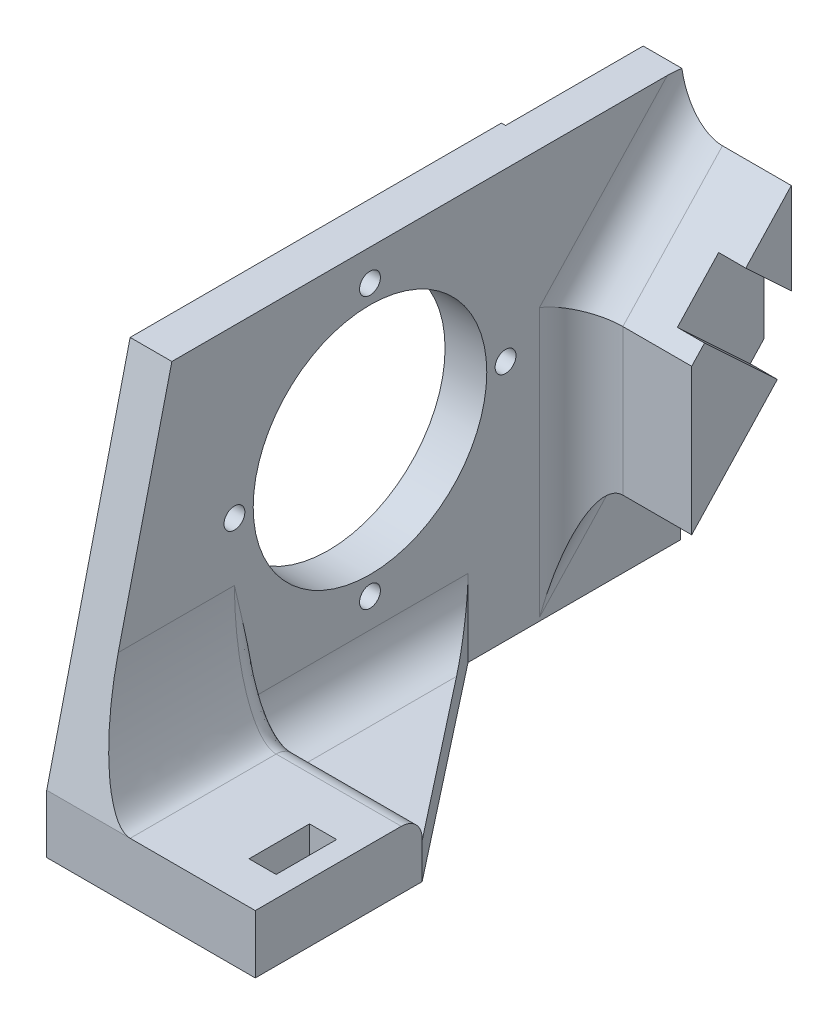
SolidWorks part; units mm, degrees
ref_plane "Front Plane" through (0, 0, 0) normal (0, 0, 1) x (1, 0, 0)
ref_plane "Top Plane" through (0, 0, 0) normal (0, 1, 0) x (1, 0, 0)
ref_plane "Right Plane" through (0, 0, 0) normal (1, 0, 0) x (0, 0, -1)
sketch "Sketch1" plane through (0, 0, 0) normal (1, 0, 0) x (0, 0, -1)
  line L1 (32.5, 0) -> (0, -32.5) construction
  line L2 (32.5, 0) -> (0, 32.5) construction
  line L3 (0, 32.5) -> (-32.5, 0) construction
  line L4 (0, -32.5) -> (-32.5, 0) construction
  line L5 (32.5, 0) -> (-32.5, 0) construction
  line L6 (0, 32.5) -> (0, -32.5) construction
  line L7 (47.5, -40) -> (-47.5, -40)
  line L8 (47.5, -40) -> (47.5, 40)
  line L9 (47.5, 40) -> (-47.5, 40)
  line L10 (-47.5, -40) -> (-47.5, 40)
  line L11 (47.5, -40) -> (-47.5, 40) construction
  line L12 (47.5, 40) -> (-47.5, -40) construction
  circle A0 centre (0, 0) radius 32.5 construction
  circle A1 centre (0, 0) radius 28
  dimension "D1" = 65
  dimension "D2" = 56
  dimension "D3" = 95
  dimension "D4" = 80
extrude "Boss-Extrude1" add sketch "Sketch1" along normal blind 10
hole_wizard "Ø5.0 (5) Diameter Hole1" positions "Sketch2" profile "Sketch3" hole size "Ø5.0" standard "ISO" end condition through all
sketch "Sketch2" plane through (10, 0, 0) normal (1, 0, 0) x (0, 0, -1)
  point P0 (-32.5, 0)
  point P3 (0, 32.5)
  point P6 (32.5, 0)
  point P9 (0, -32.5)
sketch "Sketch3" plane through (10, 0, 32.5) normal (0, 1, 0) x (0, 0, -1)
  line L0 (0, 0) -> (0, 10)
  line L1 (0, 10) -> (2.5, 10)
  line L2 (2.5, 10) -> (2.5, 0)
  line L5 (2.5, 0) -> (0, 0)
  line L11 (0, -6.35) -> (0, 107.95) construction
  dimension "Thru Hole Dia." = 5
  dimension "Thru Hole Depth" = 10
sketch "Sketch4" plane through (10, 0, 0) normal (1, 0, 0) x (0, 0, -1)
  line L0 (47.5, -40) -> (47.5, 40) construction
  line L1 (-47.5, -40) -> (47.5, -40)
  line L2 (-47.5, -40) -> (-47.5, -58)
  line L3 (-47.5, -58) -> (47.5, -58)
  line L4 (47.5, -40) -> (47.5, -58)
  dimension "D1" = 18
extrude "Boss-Extrude2" add sketch "Sketch4" against normal blind 10
sketch "Sketch5" plane through (10, 0, 0) normal (1, 0, 0) x (0, 0, -1)
  line L0 (-37.9503, -58) -> (-37.9503, -43) construction
  line L1 (-47.5, -58) -> (47.5, -58) construction
  dimension "D1" = 15
sketch "Sketch6" plane through (10, 0, 0) normal (1, 0, 0) x (0, 0, -1)
  line L1 (-47.5, -58) -> (-27.5, -58)
  line L2 (-47.5, -58) -> (-47.5, -44)
  line L3 (-47.5, -44) -> (-27.5, -44)
  line L4 (-27.5, -58) -> (-27.5, -44)
  dimension "D1" = 14
  dimension "D2" = 20
extrude "Boss-Extrude3" add sketch "Sketch6" along normal blind 40
sketch "Sketch10" plane through (0, 0, 47.5) normal (0, 0, 1) x (1, 0, 0)
  line L1 (50, -44) -> (0, -44)
  line L2 (50, -44) -> (50, -58)
  line L3 (50, -58) -> (0, -58)
  line L4 (0, -44) -> (0, -58)
extrude "Boss-Extrude4" add sketch "Sketch10" along normal blind 20
sketch "Sketch9" plane through (0, -44, 0) normal (0, 1, 0) x (1, 0, 0)
  line L0 (50, -27.5) -> (50, -67.5) construction
  line L1 (38.5, -57.5) -> (45, -57.5)
  line L2 (38.5, -57.5) -> (38.5, -43)
  line L3 (38.5, -43) -> (45, -43)
  line L4 (45, -57.5) -> (45, -43)
  line L5 (38.5, -57.5) -> (45, -43) construction
  line L6 (38.5, -43) -> (45, -57.5) construction
  line L7 (50, -67.5) -> (0, -67.5) construction
  point P0 (41.75, -50.25)
  dimension "D1" = 14.5
  dimension "D2" = 6.5
  dimension "D3" = 5
  dimension "D4" = 10
extrude "Cut-Extrude1" cut sketch "Sketch9" against normal blind 20
ref_plane "Plane2" through (5, 0, 0) normal (1, 0, 0) x (0, 0, -1)
sketch "Sketch13" plane through (5, 0, 0) normal (1, 0, 0) x (0, 0, -1)
  line L0 (-47.5, 40) -> (-67.5, -44)
  line L2 (-67.5, -44) -> (-47.5, -44)
  line L3 (-47.5, -44) -> (-47.5, 40)
extrude "Boss-Extrude5" add sketch "Sketch13" along normal mid plane 10
fillet "Fillet3" radius 10 1 edges at (10, -44, 47.5)
sketch "Sketch15" plane through (0, 0, -47.5) normal (0, 0, -1) x (-1, 0, 0)
  line L4 (0, -58) -> (0, 40)
  line L5 (0, 40) -> (-10, 40)
  line L6 (-10, 40) -> (-10, -58)
  line L7 (-10, -58) -> (0, -58)
  line L8 (0, -58) -> (0, 40)
  line L9 (0, 40) -> (-10, 40)
  line L10 (-10, 40) -> (-10, -58)
  line L11 (-10, -58) -> (0, -58)
  dimension "D1" = 0
extrude "Cut-Extrude2" cut sketch "Sketch15" against normal blind 6
sketch "Sketch16" plane through (0, 0, -41.5) normal (0, 0, -1) x (-1, 0, 0)
  line L0 (-10, -58) -> (0, -58) construction
  line L1 (-10, 40) -> (-1, 40)
  line L2 (-10, 40) -> (-10, -58)
  line L3 (-10, -58) -> (-1, -58)
  line L4 (-1, 40) -> (-1, -58)
  line L5 (0, -58) -> (0, 40) construction
  dimension "D1" = 1
extrude "Boss-Extrude7" add sketch "Sketch16" along normal blind 33
sketch "Sketch17" plane through (10, 0, 0) normal (1, 0, 0) x (0, 0, -1)
  line L0 (74.5, 40) -> (74.5, -58) construction
  line L1 (50.6274, 3.1912) -> (74.5, 28.786)
  line L2 (50.6274, 3.1912) -> (50.6274, -31.8088)
  line L3 (50.6274, -31.8088) -> (74.5, -6.214)
  line L4 (74.5, 28.786) -> (74.5, -6.214)
  line L5 (50.6274, 3.1912) -> (74.5, -6.214) construction
  line L6 (50.6274, -31.8088) -> (74.5, 28.786) construction
  point P0 (62.5637, -1.5114)
  dimension "D1" = 35
  dimension "D2" = 35
extrude "Boss-Extrude8" add sketch "Sketch17" along normal blind 26.5
sketch "Sketch18" plane through (36.5, 0, 0) normal (1, 0, 0) x (0, 0, -1)
  line L0 (53.6967, 6.4819) -> (61.0095, -0.3388)
  line L1 (74.5, 28.786) -> (50.6274, 3.1912) construction
  line L2 (61.0095, -0.3388) -> (70.8996, 10.2648)
  line L3 (70.8996, 10.2648) -> (63.5868, 17.0855)
  line L4 (74.5, 28.786) -> (50.6274, 3.1912) construction
  line L5 (63.5868, 17.0855) -> (53.6967, 6.4819)
  dimension "D1" = 14.5
  dimension "D2" = 10
  dimension "D3" = 4.5
extrude "Cut-Extrude3" cut sketch "Sketch18" against normal blind 6.5
fillet "Fillet4" radius 10 3 edges at (10, -19.0114, -62.5637) (10, -14.3088, -50.6274) (10, 15.9886, -62.5637)
sketch "Sketch19" plane through (0, -58, 0) normal (0, -1, 0) x (1, 0, 0)
  line L0 (50, 27.5) -> (10, -23.5)
  line L1 (10, -23.5) -> (10, 27.5)
  line L3 (10, 27.5) -> (50, 27.5)
  line L4 (50, 27.5) -> (10, 27.5) construction
  line L5 (10, 27.5) -> (10, -74.5) construction
extrude "Boss-Extrude9" add sketch "Sketch19" against normal blind 8.5
fillet "Fillet5" radius 5 2 edges
fillet "Fillet6" radius 10 1 edges at (10, -49.5, 2)
sketch "Sketch20" plane through (0, -30.5885, -32.7953) normal (0, 0.6821, 0.7313) x (1, 0, 0)
  line L4 (36.5, 41.3653) -> (36.5, 55.8653)
  line L5 (36.5, 55.8653) -> (30, 55.8653)
  line L6 (30, 55.8653) -> (30, 41.3653)
  line L7 (30, 41.3653) -> (36.5, 41.3653)
  line L8 (36.5, 41.3653) -> (36.5, 55.8653)
  line L9 (36.5, 55.8653) -> (30, 55.8653)
  line L10 (30, 55.8653) -> (30, 41.3653)
  line L11 (30, 41.3653) -> (36.5, 41.3653)
  dimension "D1" = 0
extrude "Cut-Extrude4" cut sketch "Sketch20" against normal through all both and the other way through all
